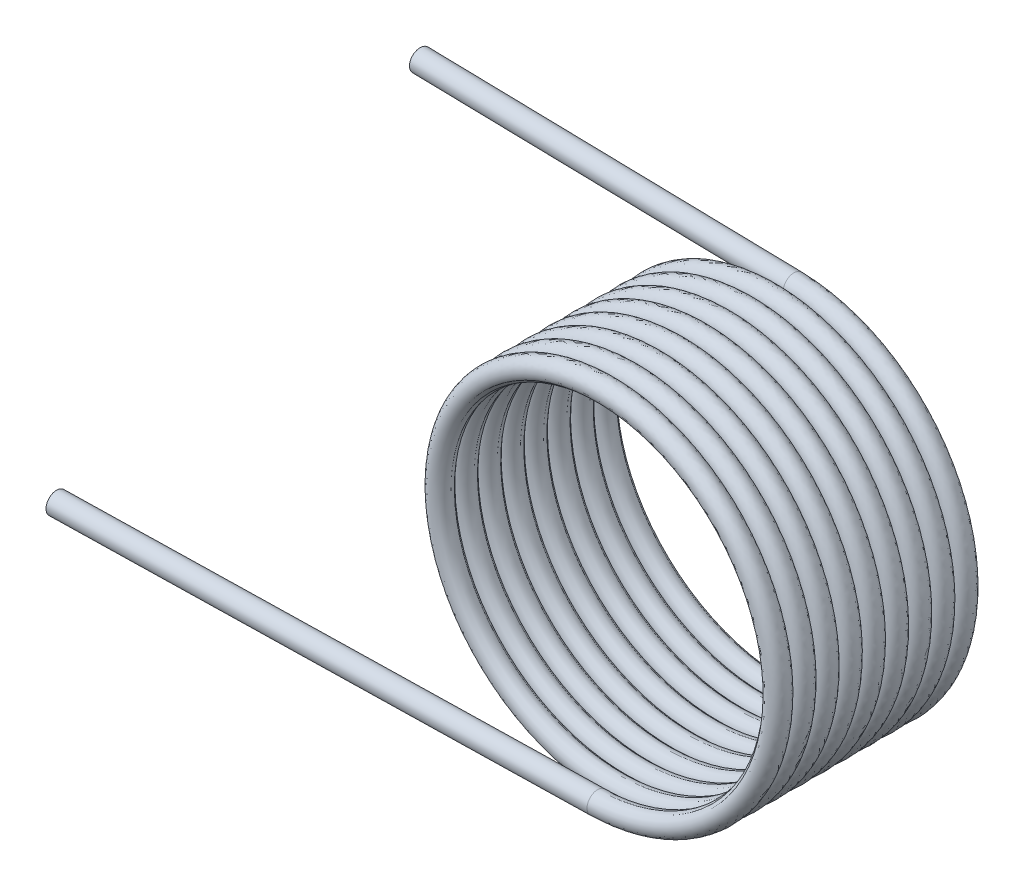
SolidWorks part; units mm, degrees
material "music wire"
ref_plane "Front Plane" through (0, 0, 0) normal (0, 0, 1) x (1, 0, 0)
ref_plane "Top Plane" through (0, 0, 0) normal (0, 1, 0) x (1, 0, 0)
ref_plane "Right Plane" through (0, 0, 0) normal (1, 0, 0) x (0, 0, -1)
sketch "Sketch1" plane through (0, 0, 0) normal (0, 0, 1) x (1, 0, 0)
  circle A0 centre (0, 0) radius 23.6029
  dimension "D1" = 47.2059
curve "Helix/Spiral1" pitch 3.1262 height 26.5723 radius 23.6029 left hand yes centre (0, 0, 0) axis (0, 0, 1) start towards (0, 1, 0)
ref_plane "Plane1" through (0, -23.6029, 26.5723) normal (-0.9998, 0, 0.0211) x (0.0211, 0, 0.9998)
sketch "Sketch2" plane through (0, -23.6029, 26.5723) normal (-0.9998, 0, 0.0211) x (0.0211, 0, 0.9998)
  circle A1 centre (0, 0) radius 1.4351
  dimension "D1" = 2.8702
sweep "Sweep1" add profiles "Sketch2" path "Helix/Spiral1"
sketch "Sketch3" plane through (0, 0, 0) normal (-0.9998, 0, -0.0211) x (-0.0211, 0, 0.9998)
  circle A0 centre (0, 23.6029) radius 1.4351 construction
  circle A1 centre (0, 23.6029) radius 1.4351
extrude "Boss-Extrude1" add sketch "Sketch3" along normal blind 101.6
sketch "Sketch4" plane through (-0.5599, 0, 0.0118) normal (-0.9998, 0, 0.0211) x (0.0211, 0, 0.9998)
  circle A0 centre (26.5664, -23.603) radius 1.4351 construction
  circle A1 centre (26.5664, -23.603) radius 1.4351
extrude "Boss-Extrude2" add sketch "Sketch4" along normal blind 101.6
sketch "Sketch5" plane through (-101.5774, 0, -2.1412) normal (-0.9998, 0, -0.0211) x (-0.0211, 0, 0.9998)
  circle A0 centre (0, 23.6029) radius 5.7146
extrude "Cut-Extrude1" cut sketch "Sketch5" against normal blind 50
sketch "Sketch6" plane through (-102.1373, 0, 2.153) normal (-0.9998, 0, 0.0211) x (0.0211, 0, 0.9998)
  circle A0 centre (26.5664, -23.6029) radius 6.6279
extrude "Cut-Extrude2" cut sketch "Sketch6" against normal blind 30
ref_axis "Axis1" through (0, 0, 24.5531) along (0, 0, -1)
